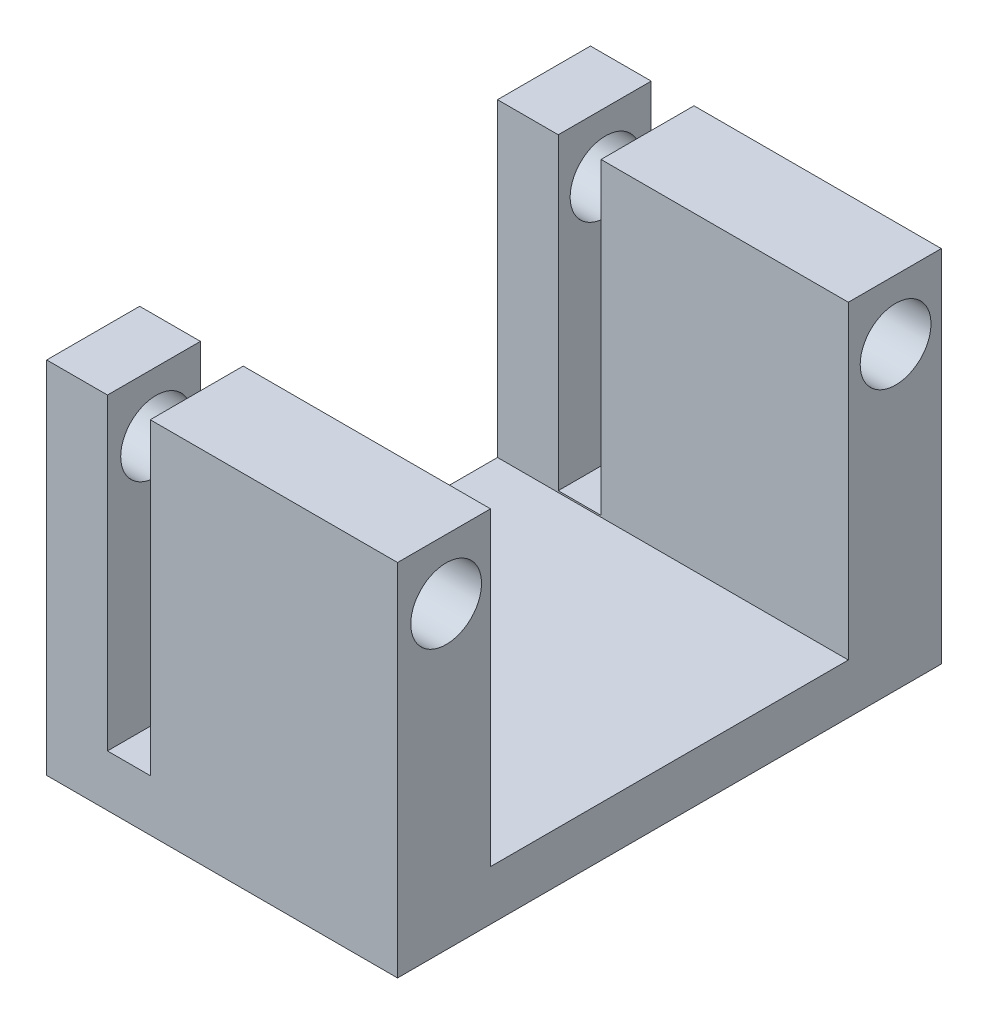
SolidWorks part; units mm, degrees
material "ABS"
ref_plane "Front Plane" through (0, 0, 0) normal (0, 0, 1) x (1, 0, 0)
ref_plane "Top Plane" through (0, 0, 0) normal (0, 1, 0) x (1, 0, 0)
ref_plane "Right Plane" through (0, 0, 0) normal (1, 0, 0) x (0, 0, -1)
sketch "Sketch1" plane through (0, 0, 0) normal (0, 1, 0) x (1, 0, 0)
  line L0 (-11.1443, 11.3665) -> (11.1443, 11.3665)
  line L1 (-11.1442, -17.272) -> (11.1443, -17.272)
  line L2 (-11.1442, -17.272) -> (-11.1443, 17.272)
  line L3 (-11.1443, 17.272) -> (11.1443, 17.272)
  line L4 (11.1443, -17.272) -> (11.1443, 17.272)
  line L5 (-11.1442, -17.272) -> (11.1443, 17.272) construction
  line L6 (-11.1443, 17.272) -> (11.1443, -17.272) construction
  line L7 (-11.1442, -11.3665) -> (11.1443, -11.3665)
  line L8 (0, -17.272) -> (0, -11.3665) construction
  line L9 (0, 17.272) -> (0, 11.3665) construction
  point P0 (0, 0)
  dimension "D1" = 22.733
  dimension "D2" = 22.2885
  dimension "D3" = 34.544
extrude "Boss-Extrude1" add sketch "Sketch1" along normal blind 3.175 contours L2 L7 L4 L0 | L0 L4 L3 L2 | L7 L2 L1 L4 region at (0, 0, -14.3193) region at (0, 0, 0) region at (0, 0, 14.3192)
extrude "Boss-Extrude2" add sketch "Sketch1<3>" along normal blind 22.86 contours L0 L4 L3 L2 | L7 L2 L1 L4 region at (0, 0, -14.3193) region at (0, 0, 14.3192)
sketch "Sketch1<3>" plane through (0, 0, 0) normal (0, 1, 0) x (1, 0, 0) same geometry as "Sketch1"
sketch "Sketch2" plane through (0, 0, -17.272) normal (0, 0, -1) x (-1, 0, 0)
  line L5 (11.1442, 22.86) -> (11.1442, 0) construction
  line L6 (4.5656, 22.86) -> (7.2834, 22.86)
  line L7 (4.5656, 22.86) -> (4.5656, 3.2783)
  line L8 (4.5656, 3.2783) -> (7.2835, 3.2783)
  line L9 (7.2834, 22.86) -> (7.2835, 3.2783)
  line L11 (11.1442, 22.86) -> (-11.1443, 22.86) construction
  dimension "D1" = 2.7178
  dimension "D3" = 6.5786
extrude "Cut-Extrude1" cut sketch "Sketch2" against normal blind 49.784 and the other way blind 17.272 contours L9 L6 L7 L8 region at (-5.9246, 13.0692, -17.272)
hole_wizard "#8 Clearance Hole1" positions "Sketch4" profile "Sketch6" hole size "#8" standard "ANSI Inch" end condition through all
sketch "Sketch4" plane through (-11.1442, 0, 0) normal (-1, 0, 0) x (0, 0, 1)
  line L0 (-11.3665, 22.86) -> (-17.272, 22.86) construction
  point P0 (-14.3679, 19.05)
  point P2 (14.1843, 19.05)
  dimension "D1" = 3.81
sketch "Sketch6" plane through (-11.1443, 19.05, -14.3679) normal (0, 1, 0) x (0, 0, 1)
  line L0 (0, 0) -> (0, 22.2885)
  line L1 (0, 22.2885) -> (2.2479, 22.2885)
  line L2 (2.2479, 22.2885) -> (2.2479, 0)
  line L5 (2.2479, 0) -> (0, 0)
  line L11 (0, -6.35) -> (0, 107.95) construction
  dimension "Thru Hole Dia." = 4.4958
  dimension "Thru Hole Depth" = 22.2885
